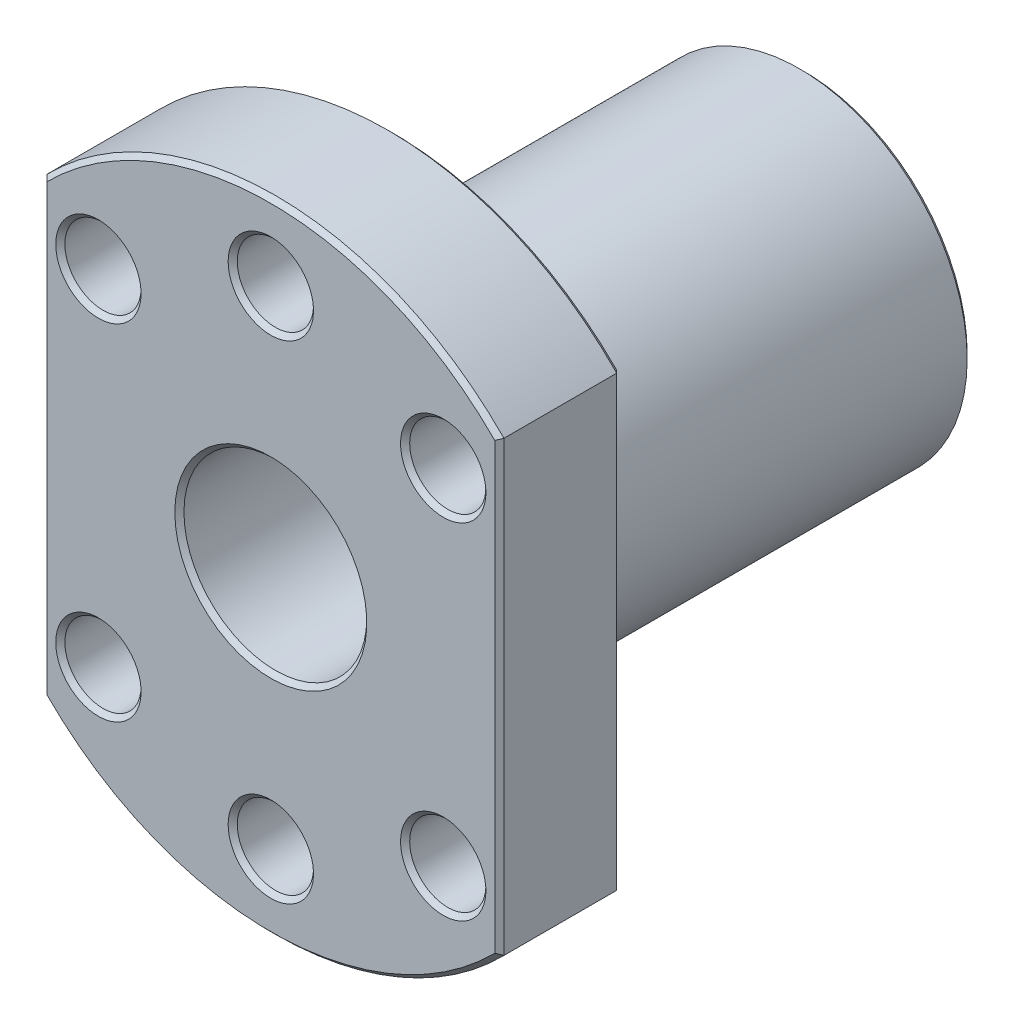
SolidWorks part; units mm, degrees
ref_plane "Front Plane" through (0, 0, 0) normal (0, 0, 1) x (1, 0, 0)
ref_plane "Top Plane" through (0, 0, 0) normal (0, 1, 0) x (1, 0, 0)
ref_plane "Right Plane" through (0, 0, 0) normal (1, 0, 0) x (0, 0, -1)
sketch "Sketch1" plane through (0, 0, 0) normal (1, 0, 0) x (0, 0, -1)
  line L0 (-27, 0) -> (-1.1455, 0) construction
  line L1 (17.5, 6) -> (-17.5, 6)
  line L2 (-17.5, 6) -> (-17.5, 21)
  line L3 (-17.5, 21) -> (-9.5, 21)
  line L4 (-9.5, 21) -> (-9.5, 11)
  line L5 (-9.5, 11) -> (17.5, 11)
  line L6 (17.5, 11) -> (17.5, 6)
  line L7 (0, 6) -> (0, 0) construction
  dimension "D1" = 27
  dimension "D2" = 8
  dimension "D3" = 21
  dimension "D4" = 12
  dimension "D5" = 22
revolve "Revolve1" add sketch "Sketch1" angle 360 about L0
sketch "Sketch2" plane through (0, 0, 0) normal (0, 1, 0) x (1, 0, 0)
  line L0 (-21, -17.5) -> (21, -17.5) construction
  line L1 (-21, -9.5) -> (-15, -9.5)
  line L2 (-21, -9.5) -> (-21, -17.5)
  line L3 (-21, -17.5) -> (-15, -17.5)
  line L4 (-15, -9.5) -> (-15, -17.5)
  line L6 (21, -9.5) -> (15, -9.5)
  line L7 (21, -9.5) -> (21, -17.5)
  line L8 (21, -17.5) -> (15, -17.5)
  line L9 (15, -9.5) -> (15, -17.5)
  dimension "D1" = 30
extrude "Cut-Extrude1" cut sketch "Sketch2" against normal through all both and the other way through all
sketch "Sketch3" plane through (0, 0, 17.5) normal (0, 0, 1) x (1, 0, 0)
  line L0 (0, 16) -> (0, 0) construction
  circle A0 centre (0, 16) radius 2.5
  circle A1 centre (11.3137, 11.3137) radius 2.5
  circle A2 centre (16, 0) radius 2.5 construction
  circle A3 centre (11.3137, -11.3137) radius 2.5
  circle A4 centre (0, -16) radius 2.5
  circle A5 centre (-11.3137, -11.3137) radius 2.5
  circle A6 centre (-16, 0) radius 2.5 construction
  circle A7 centre (-11.3137, 11.3137) radius 2.5
  point P19 (0, 0)
  dimension "D2" = 5
  dimension "D1" = 16
  dimension "D3" = 8
extrude "Cut-Extrude2" cut sketch "Sketch3" against normal blind 10
chamfer "Chamfer1" distance 0.3 angle 45 24 edges at (11, 0, 9.5) (-15, 0, 9.5) (0, -21, 9.5) (15, 0, 9.5) (0, 21, 9.5) (2.5, 16, 9.5) (-8.8137, 11.3137, 9.5) (-8.8137, -11.3137, 9.5) (2.5, -16, 9.5) (13.8137, -11.3137, 9.5) (13.8137, 11.3137, 9.5) (-15, 0, 17.5) (0, 21, 17.5) (15, 0, 17.5) (0, -21, 17.5) (6, 0, 17.5) (2.5, 16, 17.5) (-8.8137, 11.3137, 17.5) (-8.8137, -11.3137, 17.5) (2.5, -16, 17.5) (13.8137, -11.3137, 17.5) (13.8137, 11.3137, 17.5) (6, 0, -17.5) (11, 0, -17.5)
